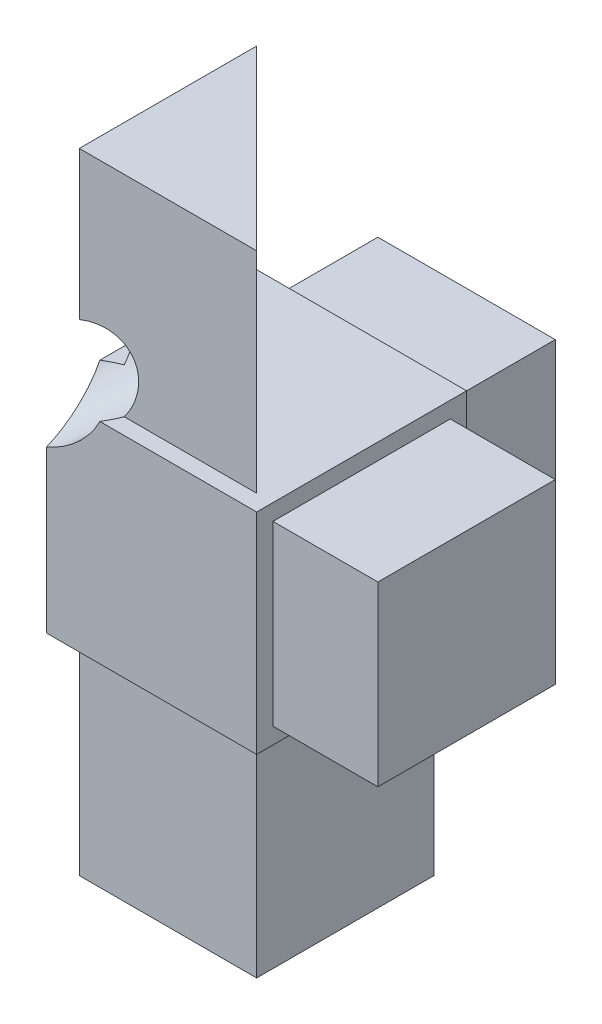
SolidWorks part; units mm, degrees
ref_plane "Front Plane" through (0, 0, 0) normal (0, 0, 1) x (1, 0, 0)
ref_plane "Top Plane" through (0, 0, 0) normal (0, 1, 0) x (1, 0, 0)
ref_plane "Right Plane" through (0, 0, 0) normal (1, 0, 0) x (0, 0, -1)
sketch "Sketch1" plane through (0, 0, 0) normal (0, 1, 0) x (1, 0, 0)
  line L0 (-8.45, 8.45) -> (8.45, 8.45)
  line L1 (-10, -10) -> (10, -10)
  line L2 (-10, -10) -> (-10, 10)
  line L3 (-10, 10) -> (10, 10)
  line L4 (10, -10) -> (10, 10)
  line L5 (-10, -10) -> (10, 10) construction
  line L6 (-10, 10) -> (10, -10) construction
  line L7 (-8.45, 10) -> (8.45, 10)
  line L8 (-8.45, 10) -> (-8.45, 20)
  line L9 (-8.45, 20) -> (8.45, 20)
  line L10 (8.45, 10) -> (8.45, 20)
  line L11 (10, 8.45) -> (20, 8.45)
  line L12 (10, 8.45) -> (10, -8.45)
  line L13 (10, -8.45) -> (20, -8.45)
  line L14 (20, 8.45) -> (20, -8.45)
  line L15 (8.45, -8.45) -> (8.45, 8.45)
  line L16 (-8.45, -8.45) -> (8.45, -8.45)
  line L17 (-8.45, -8.45) -> (-8.45, 8.45)
  line L18 (-8.45, 8.45) -> (8.45, -8.45)
  point P0 (0, 0)
  point P14 (20, 0)
  point P15 (0, 20)
  dimension "D1" = 16.9
  dimension "D2" = 10
  dimension "D3" = 20
  dimension "D4" = 20
  dimension "D5" = 1.55
extrude "Boss-Extrude1" add sketch "Sketch1" along normal blind 20 contours L1 L4 L3 L2 L16 L17 L0 L15 | L0 L18 L15 | L18 L17 L16 region at (-2.8167, 0, 2.8167) region at (2.8167, 0, -2.8167) region at (-9.7172, 0, 0)
extrude "Boss-Extrude2" add sketch "Sketch1<3>" along normal blind 16.9 from offset 1.55 contours L3 L10 L9 L8 | L14 L11 L4 L13 region at (15, 0, 0) region at (0, 0, -15)
sketch "Sketch1<3>" plane through (0, 0, 0) normal (0, 1, 0) x (1, 0, 0) same geometry as "Sketch1"
extrude "Boss-Extrude3" add sketch "Sketch1<4>" against normal blind 20 contours L18 L17 L16 | L0 L18 L15 region at (-2.8167, 0, 2.8167) region at (2.8167, 0, -2.8167)
sketch "Sketch1<4>" plane through (0, 0, 0) normal (0, 1, 0) x (1, 0, 0) same geometry as "Sketch1"
extrude "Boss-Extrude4" add sketch "Sketch1<5>" along normal blind 40 contours L18 L17 L16 region at (-2.8167, 0, 2.8167)
sketch "Sketch1<5>" plane through (0, 0, 0) normal (0, 1, 0) x (1, 0, 0) same geometry as "Sketch1"
ref_plane "Plane1" through (12.2474, 10, -12.2474) normal (0.6124, 0.5, -0.6124) x (0.7071, 0, 0.7071)
ref_plane "Plane2" through (-7.3485, -6, 7.3485) normal (0.6124, 0.5, -0.6124) x (0.7071, 0, 0.7071)
sketch "Sketch2" plane through (-7.3485, -6, 7.3485) normal (0.6124, 0.5, -0.6124) x (0.7071, 0, 0.7071)
  circle A0 centre (0, -24.3916) radius 4
  point P2 (0, 0)
  dimension "D1" = 8
extrude "Cut-Extrude1" cut sketch "Sketch2" along normal through all
